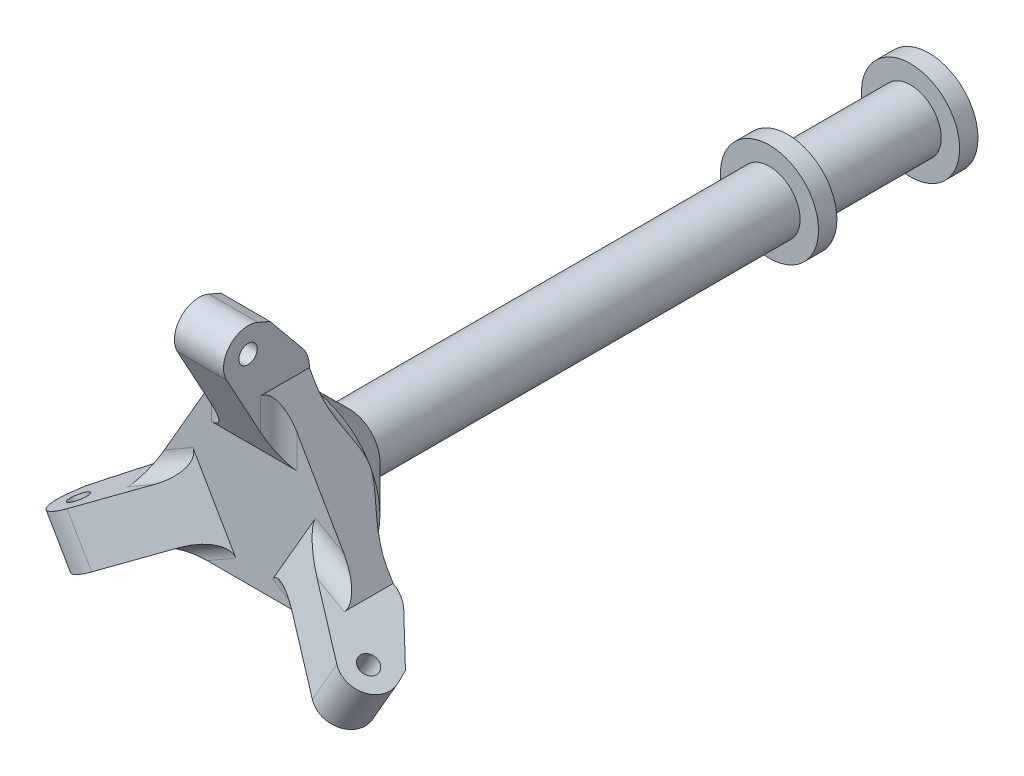
SolidWorks part; units mm, degrees
ref_plane "前视基准面" through (0, 0, 0) normal (0, 0, 1) x (1, 0, 0)
ref_plane "上视基准面" through (0, 0, 0) normal (0, 1, 0) x (1, 0, 0)
ref_plane "右视基准面" through (0, 0, 0) normal (1, 0, 0) x (0, 0, -1)
sketch "草图1" plane through (0, 0, 0) normal (1, 0, 0) x (0, 0, -1)
  line L0 (0, 37.5094) -> (0, 0) construction
  line L1 (0, 0) -> (157.6153, 0) construction
  line L2 (0, 0) -> (0, 12.5)
  line L3 (0, 12.5) -> (3, 12.5)
  line L5 (10.5, 5) -> (79, 5)
  line L6 (79, 5) -> (79, 8)
  line L7 (79, 8) -> (82, 8)
  line L8 (82, 8) -> (82, 5)
  line L9 (82, 5) -> (102, 5)
  line L10 (102, 5) -> (102, 8)
  line L11 (102, 8) -> (105, 8)
  line L12 (105, 8) -> (105, 0)
  line L13 (105, 0) -> (0, 0)
  line L14 (3, 12.5) -> (10.5, 5)
  dimension "D1" = 10
  dimension "D2" = 3
  dimension "D3" = 3
  dimension "D4" = 20
  dimension "D5" = 3
  dimension "D6" = 105
  dimension "D7" = 25
  dimension "D8" = 45
revolve "旋转1" add sketch "草图1" angle 360 about L1
sketch "草图2" plane through (0, 0, 0) normal (0, 0, 1) x (1, 0, 0)
  line L0 (0, 25) -> (0, 0) construction
  line L1 (-4, 25) -> (4, 25)
  line L2 (-4, 25) -> (-4, 18.0718)
  line L3 (19.6506, -15.9641) -> (13.6506, -12.5)
  line L4 (23.6506, -9.0359) -> (17.6506, -5.5718)
  line L5 (23.6506, -9.0359) -> (19.6506, -15.9641)
  line L6 (13.6506, -12.5) -> (-13.6506, -12.5)
  line L7 (-23.6506, -9.0359) -> (-17.6506, -5.5718)
  line L8 (-19.6506, -15.9641) -> (-23.6506, -9.0359)
  line L9 (-19.6506, -15.9641) -> (-13.6506, -12.5)
  line L10 (4, 25) -> (4, 18.0718)
  line L11 (4, 18.0718) -> (17.6506, -5.5718)
  line L12 (-17.6506, -5.5718) -> (-4, 18.0718)
  circle A0 centre (0, 0) radius 12.5 construction
  point P19 (0, 0)
  point P30 (0, 0)
  dimension "D1" = 3
  dimension "D2" = 8
  dimension "D3" = 25
  dimension "D4" = 3
extrude "凸台-拉伸1" add sketch "草图2" along normal blind 5
sketch "草图3" plane through (0, 0, 0) normal (1, 0, 0) x (0, 0, -1)
  line L0 (0, 0) -> (-20.6841, 0) construction
  line L1 (-5, 7.5) -> (-13.5105, 23.0827)
  line L2 (-5, -5.5718) -> (-5, 18.0718) construction
  line L3 (-5, 7.5) -> (-5, 25)
  line L5 (-5, 25) -> (0, 25) construction
  line L6 (-5, 25) -> (0, 25)
  line L7 (0, 25) -> (-8.4, 28.6661)
  circle A0 centre (-10, 25) radius 1.5
  arc A1 (-8.4, 28.6661) -> (-13.5105, 23.0827) centre (-10, 25) ccw
  dimension "D1" = 3
  dimension "D2" = 8
  dimension "D5" = 10
  dimension "D3" = 15
  dimension "D4" = 50
extrude "凸台-拉伸2" add sketch "草图3" along normal mid plane 8
sketch "草图5" plane through (0, 0, 0) normal (1, 0, 0) x (0, 0, -1)
  line L4 (0, 20) -> (-6.4156, 27.8)
  line L5 (0, 18.0718) -> (0, 25) construction
  line L6 (0, 25) -> (-8.4, 28.6661) construction
  line L7 (-6.4156, 27.8) -> (0, 25)
  line L8 (0, 25) -> (0, 20)
  line L9 (0, 0) -> (-13.9287, 0) construction
  dimension "D1" = 20
  dimension "D2" = 7
extrude "切除-拉伸1" cut sketch "草图5" against normal through all both and the other way through all
pattern_circular "阵列(圆周)1" count 3 over 360 about axis through (0, 0, 0) along (0, 0, 1) of "凸台-拉伸2", "切除-拉伸1"
fillet "圆角1" radius 3 6 edges at (13.0729, -2.9288, 5) (9.0729, -9.8571, 5) (-9.0729, -9.8571, 5) (-13.0729, -2.9288, 5) (-4, 12.7859, 5) (4, 12.7859, 5)
fillet "圆角2" radius 5 6 edges at (0, 12.5, 0) (10.8253, -6.25, 0) (-10.8253, -6.25, 0) (-17.3205, -10, 0) (17.3205, -10, 0) (0, 20, 0)
